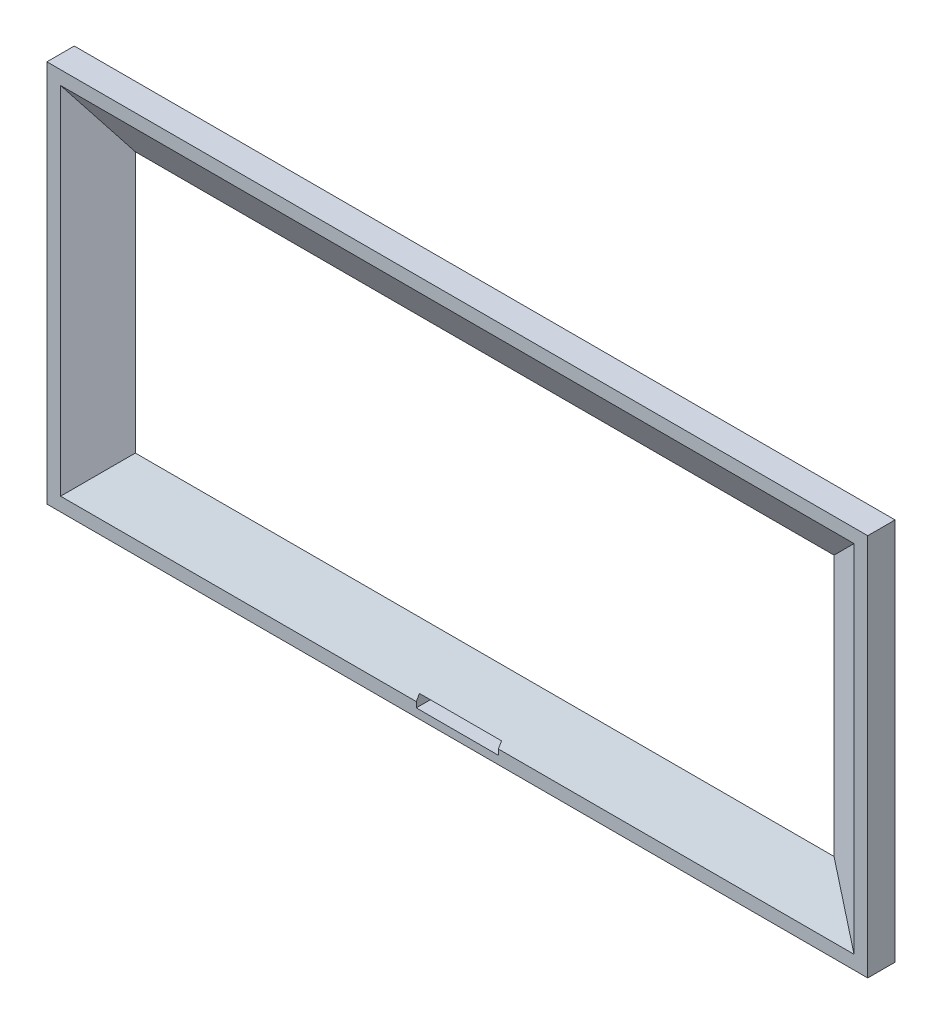
SolidWorks part; units mm, degrees
ref_plane "前视基准面" through (0, 0, 0) normal (0, 0, 1) x (1, 0, 0)
ref_plane "上视基准面" through (0, 0, 0) normal (0, 1, 0) x (1, 0, 0)
ref_plane "右视基准面" through (0, 0, 0) normal (1, 0, 0) x (0, 0, -1)
other "Configuration Table"
sketch "Sketch1" plane through (0, 0, 0) normal (0, 0, 1) x (1, 0, 0)
  line L0 (-25, -25) -> (275, -25)
  line L1 (0, 0) -> (250, 0)
  line L2 (0, 0) -> (0, 90)
  line L3 (0, 90) -> (250, 90)
  line L4 (250, 0) -> (250, 90)
  line L5 (275, -25) -> (275, 115)
  line L6 (-25, 115) -> (275, 115)
  line L7 (-25, -25) -> (-25, 115)
  dimension "D1" = 90
  dimension "D2" = 250
  dimension "D3" = 25
extrude "Boss-Extrude1" add sketch "Sketch1" along normal blind 10
chamfer "Chamfer1" distance 20 angle 30 4 edges at (250, 45, 10) (125, 90, 10) (0, 45, 10) (125, 0, 10) first distance on face at (125, 45, 10)
sketch "Sketch2" plane through (0, 0, 10) normal (0, 0, 1) x (1, 0, 0)
  line L5 (270, -20) -> (-20, -20) construction
  line L7 (140, -22) -> (110, -22)
  line L8 (140, -22) -> (140, -18)
  line L9 (140, -18) -> (110, -18)
  line L10 (110, -22) -> (110, -18)
  line L11 (140, -22) -> (110, -18) construction
  line L12 (140, -18) -> (110, -22) construction
  point P3 (125, -20)
  dimension "D1" = 30
  dimension "D2" = 4
extrude "Cut-Extrude1" cut sketch "Sketch2" against normal blind 44
